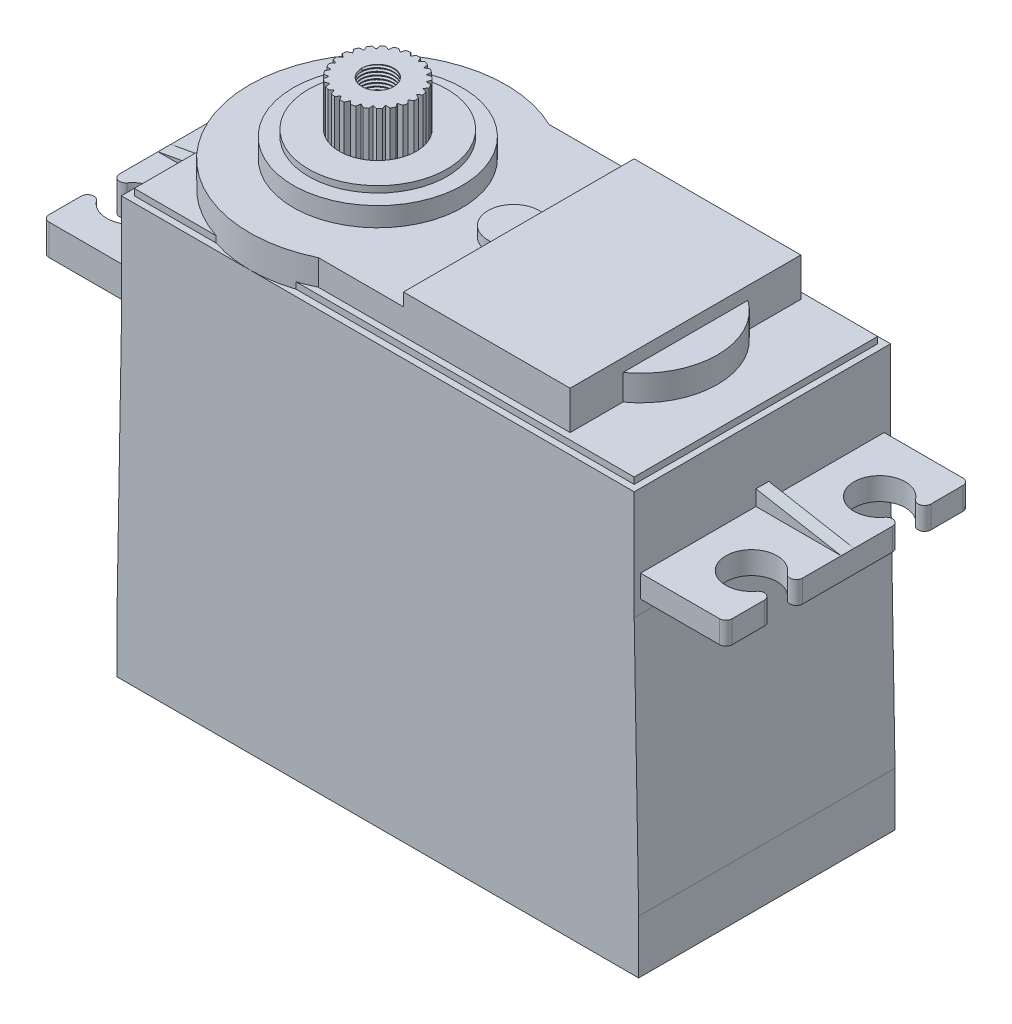
SolidWorks part; units mm, degrees
ref_plane "Front Plane" through (0, 0, 0) normal (0, 0, 1) x (1, 0, 0)
ref_plane "Top Plane" through (0, 0, 0) normal (0, 1, 0) x (1, 0, 0)
ref_plane "Right Plane" through (0, 0, 0) normal (1, 0, 0) x (0, 0, -1)
sketch "Sketch1" plane through (0, 0, 0) normal (0, 0, 1) x (1, 0, 0)
  line L0 (0, 1.994) -> (0, 0)
  line L5 (40.3491, 26.994) -> (0.3491, 26.994)
  line L7 (0, 0) -> (40.6982, 0)
  line L12 (0, 1.994) -> (0, 6.994)
  line L13 (20.3491, 35.494) -> (20.3491, 0) construction
  line L14 (40.6982, 0) -> (40.6982, 1.994)
  line L15 (40.6982, 1.994) -> (40.6982, 6.994)
  line L16 (40.6982, 6.994) -> (40.3491, 26.994)
  line L17 (40.3491, 26.994) -> (40.3491, 35.494)
  line L18 (40.3491, 35.494) -> (0.3491, 35.494)
  line L19 (0, 6.994) -> (0.3491, 26.994)
  line L20 (0.3491, 26.994) -> (0.3491, 35.494)
  point P4 (20.3491, 0)
  point P9 (20.3491, 26.994)
  dimension "D1" = 91
  dimension "D2" = 5
  dimension "D3" = 20
  dimension "D4" = 8.5
  dimension "D5" = 20
  dimension "D6" = 1.994
extrude "Body 1" add sketch "Sketch1" along normal mid plane 20 contours L5 L13 L7 L14 L15 L16 | L13 L5 L19 L12 L0 L7 | L13 L18 L20 L5 | L18 L13 L5 L17 region at (10.2389, 13.4533, 0) region at (30.4593, 13.4533, 0) region at (10.3491, 31.244, 0) region at (30.3491, 31.244, 0)
sketch "Sketch2" plane through (0, 35.494, 0) normal (0, 1, 0) x (1, 0, 0)
  line L0 (40.3491, -10) -> (0.3491, -10) construction
  line L1 (39.8491, -9.5) -> (0.8491, -9.5)
  line L2 (39.8491, -9.5) -> (39.8491, 9.5)
  line L3 (39.8491, 9.5) -> (0.8491, 9.5)
  line L4 (0.8491, -9.5) -> (0.8491, 9.5)
  line L5 (0.3491, -10) -> (0.3491, 10) construction
  line L6 (40.3491, 10) -> (0.3491, 10) construction
  line L7 (40.3491, -10) -> (40.3491, 10) construction
  dimension "D1" = 0.5
  dimension "D2" = 0.5
  dimension "D3" = 0.5
  dimension "D4" = 0.5
extrude "Boss-Extrude3" add sketch "Sketch2" along normal blind 0.5
sketch "Sketch3" plane through (0, 35.994, 0) normal (0, 1, 0) x (1, 0, 0)
  line L0 (0.3491, 0) -> (10.3491, 0)
  line L1 (0.3491, -10) -> (0.3491, 10) construction
  line L2 (39.8491, -9.5) -> (39.8491, 9.5) construction
  line L3 (14.708, -9) -> (34.3491, -9)
  line L5 (14.708, 9) -> (34.3491, 9)
  line L6 (34.3491, -9) -> (34.3491, 9)
  line L7 (0.8491, -9.5) -> (39.8491, -9.5) construction
  line L8 (39.8491, 9.5) -> (0.8491, 9.5) construction
  line L9 (39.8491, 0) -> (30.8491, 0)
  line L10 (39.8491, -9.5) -> (39.8491, 9.5) construction
  line L11 (34.3491, 4.8734) -> (34.3491, -4.8734)
  arc A0 (14.708, 9) -> (14.708, -9) centre (10.3491, 0) ccw
  arc A2 (34.3491, -4.8734) -> (34.3491, 4.8734) centre (30.8491, 0) ccw
  point P12 (39.8491, 0)
  line M4 (39.8491, 9.5) -> (0.8491, 9.5)
  line M5 (0.8491, 9.5) -> (0.8491, -9.5)
  line M6 (0.8491, -9.5) -> (39.8491, -9.5)
  dimension "D1" = 20
  dimension "D7" = 6
  dimension "D2" = 10
  dimension "D3" = 5.5
  dimension "D4" = 0.5
  dimension "D5" = 0.5
  dimension "D6" = 9
extrude "Boss-Extrude5" add sketch "Sketch3" against normal blind 0.5 contours A0 M4 | A0 L0 M5 | L0 A0 M5 | A0 M6 region at (0.6487, 35.994, -1.1749) region at (0.6487, 35.994, 1.1749) region at (10.3491, 35.994, -9.7004) region at (10.3491, 35.994, 9.7004)
sketch "Sketch8" plane through (0, 35.994, 0) normal (0, 1, 0) x (1, 0, 0)
  line L0 (0.3491, 0) -> (10.3491, 0)
  line L1 (14.708, -9) -> (34.3491, -9)
  line L2 (14.708, 9) -> (34.3491, 9)
  line L3 (34.3491, -9) -> (34.3491, 9)
  line L4 (39.8491, 0) -> (30.8491, 0)
  line L6 (39.8491, -9.5) -> (39.8491, 9.5) construction
  line L7 (0.3491, -10) -> (0.3491, 10) construction
  line L8 (34.3491, -4.8734) -> (34.3491, 4.8734)
  arc A0 (14.708, 9) -> (14.708, -9) centre (10.3491, 0) ccw
  arc A2 (34.3491, -4.8734) -> (34.3491, 4.8734) centre (30.8491, 0) ccw
  arc M11 (13.4716, 9.5) -> (7.2266, 9.5) centre (10.3491, 0) ccw
  arc M14 (0.8491, 3.1225) -> (0.8491, -3.1225) centre (10.3491, 0) ccw
  arc M17 (7.2266, -9.5) -> (13.4716, -9.5) centre (10.3491, 0) ccw
  dimension "D1" = 20
  dimension "D4" = 19.6411
  dimension "D7" = 12
  dimension "D2" = 10
  dimension "D3" = 18
  dimension "D5" = 5.5
  dimension "D6" = 9
extrude "Boss-Extrude6" add sketch "Sketch8" along normal blind 2 contours L4 A2 L3 | L3 A2 L4 | A0 L1 L3 L2 M14 M17 M11 region at (17.9581, 35.994, 0) region at (35.3694, 35.994, 1.8917) region at (35.3694, 35.994, -1.8917)
sketch "Sketch11" plane through (0, 37.994, 0) normal (0, 1, 0) x (1, 0, 0)
  line L10 (14.708, -9) -> (34.3491, -9) construction
  line L11 (34.3491, 9) -> (21.3491, 9)
  line L12 (34.3491, 9) -> (34.3491, -9)
  line L13 (34.3491, -9) -> (21.3491, -9)
  line L14 (21.3491, 9) -> (21.3491, -9)
  dimension "D1" = 13
extrude "Boss-Extrude7" add sketch "Sketch11" along normal blind 1
sketch "Sketch12" plane through (0, 37.994, 0) normal (0, 1, 0) x (1, 0, 0)
  line L0 (20.9491, 0) -> (21.3491, 0)
  line L1 (21.3491, 9) -> (21.3491, -9) construction
  line L2 (21.3491, -1.9596) -> (21.3491, 1.9596)
  arc A0 (21.3491, 1.9596) -> (21.3491, -1.9596) centre (20.9491, 0) ccw
  line M4 (21.3491, -9) -> (21.3491, 9)
  dimension "D1" = 4
  dimension "D2" = 0.4
  dimension "D3" = 3.9192
extrude "Boss-Extrude8" add sketch "Sketch12" along normal blind 0.8 contours A0 M4 region at (20.3119, 37.994, 0)
sketch "Sketch13" plane through (0, 37.994, 0) normal (0, 1, 0) x (1, 0, 0)
  circle A0 centre (10.3491, 0) radius 6.6
  dimension "D1" = 13.2
extrude "Boss-Extrude9" add sketch "Sketch13" along normal blind 1.5
sketch "Sketch14" plane through (0, 39.494, 0) normal (0, 1, 0) x (1, 0, 0)
  circle A0 centre (10.3491, 0) radius 5.4
  dimension "D1" = 10.8
extrude "Boss-Extrude10" add sketch "Sketch14" along normal blind 0.5
sketch "Sketch17" plane through (0, 39.994, 0) normal (0, 1, 0) x (1, 0, 0)
  line L0 (15.7491, 0) -> (4.9491, 0) construction
  circle A0 centre (10.3491, 0) radius 5.4 construction
  circle A1 centre (10.3491, 0) radius 3
  dimension "D1" = 6
extrude "Cut-Extrude1" cut sketch "Sketch17" against normal blind 12
chamfer "Chamfer2" distance 2.82 angle 45 4 edges at (20.3491, 0, -10) (40.6982, 0, 0) (20.3491, 0, 10) (0, 0, 0)
hole_wizard "CBORE for M2 Pan Head Machine Screw1" positions "Sketch19" profile "Sketch20" counterbore size "M2" standard "ANSI Metric"
sketch "Sketch19" plane through (0, 0, 0) normal (0, -1, 0) x (-1, 0, 0)
  line L0 (-40.6982, -10) -> (-40.6982, 10) construction
  line L1 (0, 10) -> (-40.6982, 10) construction
  line L2 (0, -10) -> (0, 10) construction
  line L3 (0, -10) -> (-40.6982, -10) construction
  point P0 (-38.6982, 8)
  point P2 (-2, 8)
  point P4 (-2, -8)
  point P6 (-38.6982, -8)
  dimension "D1" = 2
  dimension "D2" = 2
  dimension "D3" = 2
  dimension "D4" = 2
sketch "Sketch20" plane through (38.6982, 0, -8) normal (1, 0, 0) x (0, 0, -1)
  line L0 (0, 0) -> (0, 8.721)
  line L1 (0, 8.721) -> (1.2, 8)
  line L2 (1.2, 8) -> (1.2, 1.6)
  line L3 (1.2, 1.6) -> (2.5, 1.6)
  line L4 (2.5, 1.6) -> (2.5, 0)
  line L5 (2.5, 0) -> (0, 0)
  line L10 (0, 8.721) -> (-1.2, 8) construction
  line L11 (0, -6.35) -> (0, 107.95) construction
  dimension "Hole Dia." = 2.4
  dimension "Hole Depth" = 8
  dimension "C'Bore Dia." = 5
  dimension "C'Bore Depth" = 1.6
  dimension "Drill Angle" = 118
sketch "Sketch21" plane through (0, 27.994, 0) normal (0, 1, 0) x (1, 0, 0)
  circle A0 centre (10.3491, 0) radius 3
extrude "Boss-Extrude11" add sketch "Sketch21" along normal blind 10.5 separate body
sketch "Sketch22" plane through (0, 38.494, 0) normal (0, 1, 0) x (1, 0, 0)
  line L0 (10.3491, 0) -> (7.6491, 0)
  line L1 (7.6491, 0) -> (7.3582, -0.212)
  line L2 (7.3582, -0.212) -> (7.3582, 0.212)
  line L3 (7.3582, 0.212) -> (7.6491, 0)
  line L4 (7.7339, 0.6715) -> (7.3994, 0.5384)
  line L5 (7.3994, 0.5384) -> (7.5049, 0.9492)
  line L6 (7.5049, 0.9492) -> (7.7339, 0.6715)
  line L7 (7.9831, 1.3007) -> (7.626, 1.2551)
  line L8 (7.626, 1.2551) -> (7.8303, 1.6267)
  line L9 (7.8303, 1.6267) -> (7.9831, 1.3007)
  line L10 (8.3809, 1.8483) -> (8.0237, 1.8929)
  line L11 (8.0237, 1.8929) -> (8.314, 2.202)
  line L12 (8.314, 2.202) -> (8.3809, 1.8483)
  line L13 (8.9024, 2.2797) -> (8.5675, 2.4117)
  line L14 (8.5675, 2.4117) -> (8.9255, 2.6389)
  line L15 (8.9255, 2.6389) -> (8.9024, 2.2797)
  line L16 (9.5148, 2.5679) -> (9.2232, 2.779)
  line L17 (9.2232, 2.779) -> (9.6265, 2.9101)
  line L18 (9.6265, 2.9101) -> (9.5148, 2.5679)
  line L19 (10.1796, 2.6947) -> (9.9497, 2.9717)
  line L20 (9.9497, 2.9717) -> (10.3729, 2.9983)
  line L21 (10.3729, 2.9983) -> (10.1796, 2.6947)
  line L22 (10.855, 2.6522) -> (10.7013, 2.9777)
  line L23 (10.7013, 2.9777) -> (11.1178, 2.8982)
  line L24 (11.1178, 2.8982) -> (10.855, 2.6522)
  line L25 (11.4987, 2.443) -> (11.4307, 2.7966)
  line L26 (11.4307, 2.7966) -> (11.8144, 2.616)
  line L27 (11.8144, 2.616) -> (11.4987, 2.443)
  line L28 (12.0701, 2.0804) -> (12.0922, 2.4397)
  line L29 (12.0922, 2.4397) -> (12.419, 2.1694)
  line L30 (12.419, 2.1694) -> (12.0701, 2.0804)
  line L31 (12.5334, 1.587) -> (12.6442, 1.9296)
  line L32 (12.6442, 1.9296) -> (12.8934, 1.5865)
  line L33 (12.8934, 1.5865) -> (12.5334, 1.587)
  line L34 (12.8595, 0.9939) -> (13.0519, 1.2982)
  line L35 (13.0519, 1.2982) -> (13.2081, 0.9039)
  line L36 (13.2081, 0.9039) -> (12.8595, 0.9939)
  line L37 (13.0278, 0.3384) -> (13.2899, 0.5852)
  line L38 (13.2899, 0.5852) -> (13.343, 0.1645)
  line L39 (13.343, 0.1645) -> (13.0278, 0.3384)
  line L40 (13.0278, -0.3384) -> (13.343, -0.1645)
  line L41 (13.343, -0.1645) -> (13.2899, -0.5852)
  line L42 (13.2899, -0.5852) -> (13.0278, -0.3384)
  line L43 (12.8595, -0.9939) -> (13.2081, -0.9039)
  line L44 (13.2081, -0.9039) -> (13.0519, -1.2982)
  line L45 (13.0519, -1.2982) -> (12.8595, -0.9939)
  line L46 (12.5334, -1.587) -> (12.8934, -1.5865)
  line L47 (12.8934, -1.5865) -> (12.6442, -1.9296)
  line L48 (12.6442, -1.9296) -> (12.5334, -1.587)
  line L49 (12.0701, -2.0804) -> (12.419, -2.1694)
  line L50 (12.419, -2.1694) -> (12.0922, -2.4397)
  line L51 (12.0922, -2.4397) -> (12.0701, -2.0804)
  line L52 (11.4987, -2.443) -> (11.8144, -2.616)
  line L53 (11.8144, -2.616) -> (11.4307, -2.7966)
  line L54 (11.4307, -2.7966) -> (11.4987, -2.443)
  line L55 (10.855, -2.6522) -> (11.1178, -2.8982)
  line L56 (11.1178, -2.8982) -> (10.7013, -2.9777)
  line L57 (10.7013, -2.9777) -> (10.855, -2.6522)
  line L58 (10.1796, -2.6947) -> (10.3729, -2.9983)
  line L59 (10.3729, -2.9983) -> (9.9497, -2.9717)
  line L60 (9.9497, -2.9717) -> (10.1796, -2.6947)
  line L61 (9.5148, -2.5679) -> (9.6265, -2.9101)
  line L62 (9.6265, -2.9101) -> (9.2232, -2.779)
  line L63 (9.2232, -2.779) -> (9.5148, -2.5679)
  line L64 (8.9024, -2.2797) -> (8.9255, -2.6389)
  line L65 (8.9255, -2.6389) -> (8.5675, -2.4117)
  line L66 (8.5675, -2.4117) -> (8.9024, -2.2797)
  line L67 (8.3809, -1.8483) -> (8.314, -2.202)
  line L68 (8.314, -2.202) -> (8.0237, -1.8929)
  line L69 (8.0237, -1.8929) -> (8.3809, -1.8483)
  line L70 (7.9831, -1.3007) -> (7.8303, -1.6267)
  line L71 (7.8303, -1.6267) -> (7.626, -1.2551)
  line L72 (7.626, -1.2551) -> (7.9831, -1.3007)
  line L73 (7.7339, -0.6715) -> (7.5049, -0.9492)
  line L74 (7.5049, -0.9492) -> (7.3994, -0.5384)
  line L75 (7.3994, -0.5384) -> (7.7339, -0.6715)
  circle A3 centre (10.3491, 0) radius 2.9984
  dimension "D2" = 2.7
  dimension "D3" = 72.17
  dimension "D4" = 25
  dimension "D1" = 0.36
extrude "Boss-Extrude16" add sketch "Sketch22" along normal blind 5 contours L58 A3 L57 L55 L54 L52 L51 L49 L48 L46 L45 L43 L42 L40 L39 L37 L36 L34 L33 L31 L30 L28 L27 L25 L24 L22 L21 L19 L18 L16 L15 L13 L12 L10 L9 region at (7.5536, 38.494, -0.1745)
sketch "Sketch23" plane through (40.3491, 0, 0) normal (1, 0, 0) x (0, 0, -1)
  line L0 (-10, 26.994) -> (10, 26.994) construction
  line L1 (-9.5, 29.748) -> (9.5, 29.748)
  line L2 (-9.5, 29.748) -> (-9.5, 27.994)
  line L3 (-9.5, 27.994) -> (9.5, 27.994)
  line L4 (9.5, 29.748) -> (9.5, 27.994)
  line L5 (-10, 26.994) -> (-10, 35.494) construction
  line L7 (-9.5, 35.494) -> (9.5, 35.494) construction
  dimension "D1" = 19
  dimension "D2" = 1
  dimension "D3" = 0.5
  dimension "D4" = 5.746
extrude "Boss-Extrude17" add sketch "Sketch23" along normal blind 6.65
fillet "Fillet1" radius 0.5 2 edges at (46.9991, 28.871, 9.5) (46.9991, 28.871, -9.5)
sketch "Sketch25" plane through (0, 29.748, 0) normal (0, 1, 0) x (1, 0, 0)
  line L0 (40.3491, 0) -> (46.9991, 0) construction
  line L1 (40.3491, 9.5) -> (46.4991, 9.5)
  line L2 (40.3491, 9.5) -> (40.3491, -9.5)
  line L3 (40.3491, -9.5) -> (46.4991, -9.5)
  line L4 (46.9991, 9) -> (46.9991, -9)
  line L5 (42.4991, 5) -> (46.4991, 5) construction
  line L6 (46.9991, 6.5) -> (46.9991, 3.5)
  line L7 (46.9991, -3.5) -> (46.9991, -6.5)
  arc A0 (46.9991, -9) -> (46.4991, -9.5) centre (46.4991, -9) cw
  arc A1 (46.9991, 9) -> (46.4991, 9.5) centre (46.4991, 9) ccw
  arc A2 (46.0991, 6.2) -> (46.0991, 3.8) centre (44.4991, 5) ccw
  arc A4 (46.0991, 6.2) -> (46.9991, 6.5) centre (46.4991, 6.5) ccw
  arc A5 (46.0991, 3.8) -> (46.9991, 3.5) centre (46.4991, 3.5) cw
  arc A6 (46.0991, -3.8) -> (46.9991, -3.5) centre (46.4991, -3.5) ccw
  arc A7 (46.0991, -6.2) -> (46.9991, -6.5) centre (46.4991, -6.5) cw
  arc A8 (46.0991, -6.2) -> (46.0991, -3.8) centre (44.4991, -5) cw
  point P7 (46.9991, -9.5)
  point P10 (46.9991, 9.5)
  dimension "D3" = 0.5
  dimension "D4" = 4
  dimension "D5" = 1
  dimension "D6" = 4.15
  dimension "D7" = 4.5
  dimension "D1" = 6.65
  dimension "D2" = 19
extrude "Cut-Extrude2" cut sketch "Sketch25" against normal blind 7 contours L6 A5 A2 A4 | A6 L7 A7 A8
sketch "Sketch26" plane through (40.3491, 0, 0) normal (1, 0, 0) x (0, 0, -1)
  line L0 (0, 29.748) -> (0, 30.948) construction
  line L1 (9.5, 29.748) -> (-9.5, 29.748) construction
  line L2 (-0.5, 30.948) -> (0.5, 30.948)
  line L3 (0.5, 30.948) -> (0.5, 29.748)
  line L4 (3.5, 29.748) -> (-3.5, 29.748) construction
  line L5 (-0.5, 30.948) -> (-0.5, 29.748)
  line L6 (-0.5, 29.748) -> (0.5, 29.748)
  dimension "D1" = 0.5
  dimension "D2" = 1.2
extrude "Boss-Extrude18" add sketch "Sketch26" along normal blind 6.65
sketch "Sketch28" plane through (0, 0, 0.5) normal (0, 0, 1) x (1, 0, 0)
  line L0 (40.3491, 30.948) -> (46.9991, 29.748)
  line L1 (46.9991, 29.748) -> (46.9991, 30.948)
  line L2 (46.9991, 30.948) -> (40.3491, 30.948)
extrude "Cut-Extrude3" cut sketch "Sketch28" against normal blind 6.65
sketch "Sketch29" plane through (0.3491, 0, 0) normal (-1, 0, 0) x (0, 0, 1)
  line L0 (-9.5, 30.394) -> (-0.5, 30.394)
  line L1 (-10, 26.994) -> (-10, 35.494) construction
  line L3 (-9.5, 30.394) -> (-9.5, 27.994)
  line L4 (-9.5, 27.994) -> (9.5, 27.994)
  line L5 (9.5, 30.394) -> (9.5, 27.994)
  line L11 (10, 26.994) -> (-10, 26.994) construction
  line L14 (-0.5, 31.594) -> (0.5, 31.594)
  line L15 (0.5, 31.594) -> (0.5, 30.394)
  line L17 (-0.5, 31.594) -> (-0.5, 30.394)
  line L18 (0.5, 30.394) -> (9.5, 30.394)
  dimension "D1" = 19
  dimension "D2" = 0.5
  dimension "D3" = 2.4
  dimension "D4" = 1
  dimension "D5" = 1.2
  dimension "D6" = 1
  dimension "D7" = 9
  dimension "D8" = 9
extrude "Boss-Extrude19" add sketch "Sketch29" along normal blind 6.65
sketch "Sketch30" plane through (0, 0, -0.5) normal (0, 0, -1) x (-1, 0, 0)
  line L0 (-0.3491, 31.594) -> (6.3009, 30.394)
  line L1 (6.3009, 30.394) -> (6.3009, 31.594)
  line L2 (6.3009, 31.594) -> (-0.3491, 31.594)
extrude "Cut-Extrude4" cut sketch "Sketch30" against normal blind 6.65
sketch "Sketch31" plane through (0, 27.994, 0) normal (0, -1, 0) x (1, 0, 0)
  line L1 (0.3491, -9.5) -> (-5.8009, -9.5)
  line L2 (0.3491, -9.5) -> (0.3491, 9.5)
  line L3 (0.3491, 9.5) -> (-5.8009, 9.5)
  line L4 (-6.3009, -9) -> (-6.3009, 9)
  line L5 (0, 0) -> (-6.3009, 0) construction
  line L6 (-6.3009, -6.5) -> (-6.3009, -3.5)
  line L7 (-1.8009, -5) -> (-5.8009, -5) construction
  line L8 (-6.3009, 6.5) -> (-6.3009, 3.5)
  arc A0 (-5.8009, 9.5) -> (-6.3009, 9) centre (-5.8009, 9) ccw
  arc A1 (-5.8009, -9.5) -> (-6.3009, -9) centre (-5.8009, -9) cw
  arc A2 (-5.4009, -6.2) -> (-5.4009, -3.8) centre (-3.8009, -5) ccw
  arc A3 (-5.4009, -6.2) -> (-6.3009, -6.5) centre (-5.8009, -6.5) ccw
  arc A4 (-5.4009, -3.8) -> (-6.3009, -3.5) centre (-5.8009, -3.5) cw
  arc A5 (-5.4009, 3.8) -> (-6.3009, 3.5) centre (-5.8009, 3.5) ccw
  arc A6 (-5.4009, 6.2) -> (-5.4009, 3.8) centre (-3.8009, 5) cw
  arc A7 (-5.4009, 6.2) -> (-6.3009, 6.5) centre (-5.8009, 6.5) cw
  point P8 (-6.3009, 9.5)
  dimension "D1" = 0.5
  dimension "D2" = 4
  dimension "D3" = 1
  dimension "D4" = 4.5
  dimension "D5" = 2.5
extrude "Cut-Extrude6" cut sketch "Sketch31" against normal blind 6.65 contours A2 A4 L6 A3 | A6 A5 L8 A7
fillet "Fillet2" radius 0.5 2 edges at (-6.3009, 29.194, -9.5) (-6.3009, 29.194, 9.5)
sketch "Sketch34" plane through (0, 43.494, 0) normal (0, 1, 0) x (1, 0, 0)
  circle A0 centre (10.3491, 0) radius 1.25
  dimension "D1" = 2.5
extrude "Cut-Extrude7" cut sketch "Sketch34" against normal blind 8
thread "Thread1" pitch 0.25 method cut profile "Thread Profile1" start angle 0, offset 0, length 8, pitch 0.25, diameter 2.5
ref_plane "Plane2" through (9.0991, 43.494, 0) normal (0, 0, 1) x (-1, 0, 0)
sketch "Thread Profile1" plane through (9.0991, 43.494, 0) normal (0, 0, 1) x (-1, 0, 0)
  line L0 (0, 0) -> (0, 0.25) construction
  line L1 (0, 0) -> (0.1353, 0.0781)
  line L2 (0.1353, 0.0781) -> (0.1353, 0.1094)
  line L3 (0.1353, 0.1094) -> (0, 0.1875)
  line L4 (0.1353, 0.0937) -> (0, 0.0937) construction
  line L11 (0, 0) -> (0, 0.1875)
  point P2 (0, 0)
  dimension "Pitch" = 0.25
  dimension "Profile_Angle" = 60
  dimension "Profile_Land" = 0.0312
  dimension "Profile_Height" = 0.1353
